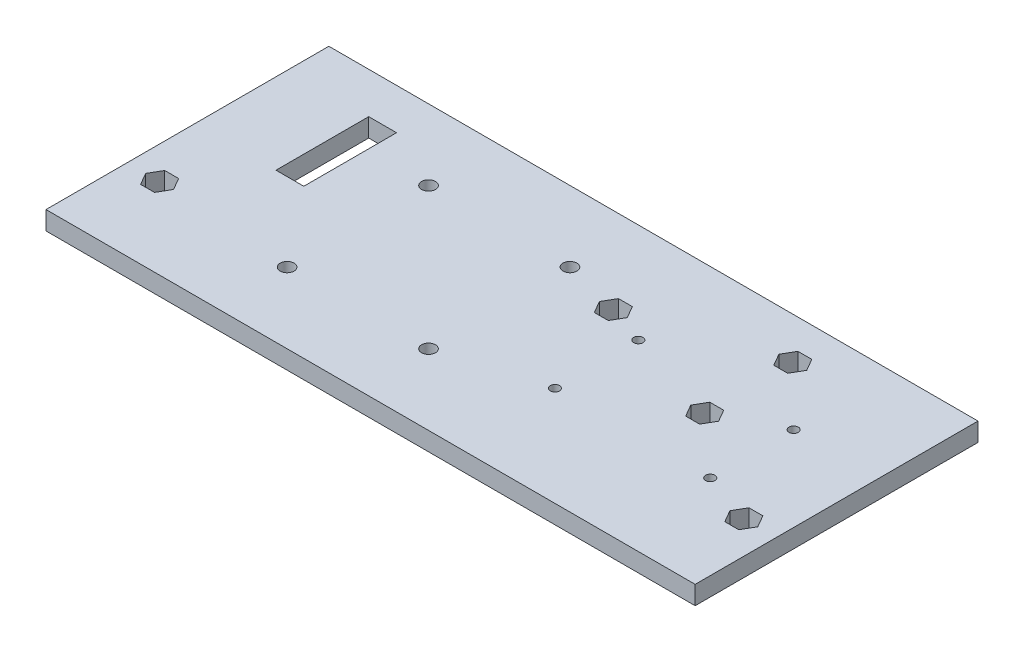
SolidWorks part; units mm, degrees
material "Balsa"
ref_plane "Ebene vorne" through (0, 0, 0) normal (0, 0, 1) x (1, 0, 0)
ref_plane "Ebene oben" through (0, 0, 0) normal (0, 1, 0) x (1, 0, 0)
ref_plane "Ebene rechts" through (0, 0, 0) normal (1, 0, 0) x (0, 0, -1)
sketch "Sketch1" plane through (0, 0, 0) normal (0, 1, 0) x (1, 0, 0)
  line L0 (-24.1206, 0) -> (93.4673, 0) construction
  line L2 (0, 30.5) -> (140, 30.5)
  line L3 (0, 30.5) -> (0, -30.5)
  line L4 (0, -30.5) -> (140, -30.5)
  line L5 (140, 30.5) -> (140, -30.5)
  dimension "D1" = 61
  dimension "D2" = 140
extrude "Boss-Extrude1" add sketch "Sketch1" along normal blind 4
sketch "Sketch2" plane through (0, 4, 0) normal (0, 1, 0) x (1, 0, 0)
  line L1 (17.4497, 21.6501) -> (23.4497, 21.6501)
  line L2 (17.4497, 21.6501) -> (17.4497, 1.6501)
  line L3 (17.4497, 1.6501) -> (23.4497, 1.6501)
  line L4 (23.4497, 21.6501) -> (23.4497, 1.6501)
  dimension "D1" = 20
  dimension "D2" = 6
extrude "Cut-Extrude1" cut sketch "Sketch2" against normal blind 10 contours L4 L3 L2 L1
sketch "Sketch4" plane through (0, 0, 0) normal (0, -1, 0) x (1, 0, 0)
  circle A0 centre (88.25, -9) radius 1
  circle A1 centre (88.25, 9) radius 1
  circle A2 centre (121.75, -9) radius 1
  circle A3 centre (121.75, 9) radius 1
  circle A4 centre (36.75, 15.25) radius 1.5
  circle A5 centre (67.25, 15.25) radius 1.5
  circle A6 centre (67.25, -15.25) radius 1.5
  circle A7 centre (36.75, -15.25) radius 1.5
  dimension "D1" = 3
  dimension "D2" = 2
extrude "Cut-Extrude2" [suppressed] cut sketch "Sketch4" against normal blind 4 contours A5
extrude "Cut-Extrude3" cut sketch "Sketch4<3>" against normal blind 4
sketch "Sketch4<3>" plane through (0, 0, 0) normal (0, -1, 0) x (1, 0, 0) same geometry as "Sketch4"
sketch "Sketch6" plane through (0, 4, 0) normal (0, 1, 0) x (1, 0, 0)
  line L0 (0, 0) -> (140, 0) construction
  line L1 (81.3585, 14.6) -> (78.3563, 14.6)
  line L2 (78.3563, 14.6) -> (76.8552, 12)
  line L3 (76.8552, 12) -> (78.3563, 9.4)
  line L4 (78.3563, 9.4) -> (81.3585, 9.4)
  line L5 (81.3585, 9.4) -> (82.8597, 12)
  line L6 (82.8597, 12) -> (81.3585, 14.6)
  line L7 (140, -30.5) -> (140, 30.5) construction
  line L9 (110.5585, 5.1) -> (107.5563, 5.1)
  line L10 (107.5563, 5.1) -> (106.0552, 2.5)
  line L11 (106.0552, 2.5) -> (107.5563, -0.1)
  line L12 (107.5563, -0.1) -> (110.5585, -0.1)
  line L13 (110.5585, -0.1) -> (112.0597, 2.5)
  line L14 (112.0597, 2.5) -> (110.5585, 5.1)
  line L15 (112.0597, 21.5) -> (110.5585, 24.1)
  line L16 (110.5585, 24.1) -> (107.5563, 24.1)
  line L17 (107.5563, 24.1) -> (106.0552, 21.5)
  line L18 (106.0552, 21.5) -> (107.5563, 18.9)
  line L19 (107.5563, 18.9) -> (110.5585, 18.9)
  line L20 (110.5585, 18.9) -> (112.0597, 21.5)
  circle A0 centre (109.0574, 2.5) radius 2.6 construction
  circle A3 centre (79.8574, 12) radius 2.6 construction
  circle A4 centre (109.0574, 21.5) radius 2.6 construction
  point P9 (79.8574, 9.4)
  dimension "D2" = 5.2
extrude "Cut-Extrude4" cut sketch "Sketch6" against normal blind 34
sketch "Sketch7" plane through (0, 4, 0) normal (0, 1, 0) x (1, 0, 0)
  line L1 (10.0022, -13) -> (8.5011, -10.4)
  line L2 (8.5011, -10.4) -> (5.4989, -10.4)
  line L3 (5.4989, -10.4) -> (3.9978, -13)
  line L4 (3.9978, -13) -> (5.4989, -15.6)
  line L5 (5.4989, -15.6) -> (8.5011, -15.6)
  line L6 (8.5011, -15.6) -> (10.0022, -13)
  line L7 (136.0022, -13) -> (134.5011, -10.4)
  line L8 (134.5011, -10.4) -> (131.4989, -10.4)
  line L9 (131.4989, -10.4) -> (129.9978, -13)
  line L10 (129.9978, -13) -> (131.4989, -15.6)
  line L11 (131.4989, -15.6) -> (134.5011, -15.6)
  line L12 (134.5011, -15.6) -> (136.0022, -13)
  circle A1 centre (133, -13) radius 2.6 construction
  circle A2 centre (7, -13) radius 2.6 construction
  dimension "D1" = 5.2
  dimension "D2" = 5.2
extrude "Cut-Extrude5" cut sketch "Sketch7" against normal blind 10
ref_plane "Plane1" through (136.0022, 4, 13) normal (-0.5, 0, -0.866) x (-0.866, 0, 0.5)
